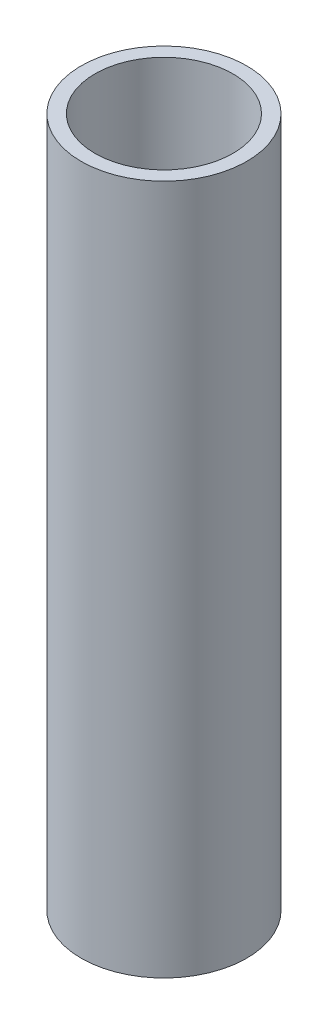
SolidWorks part; units mm, degrees
material "AISI 304"
ref_plane "Спереди" through (0, 0, 0) normal (0, 0, 1) x (1, 0, 0)
ref_plane "Сверху" through (0, 0, 0) normal (0, 1, 0) x (1, 0, 0)
ref_plane "Справа" through (0, 0, 0) normal (1, 0, 0) x (0, 0, -1)
ref_axis "ОсьX" through (-88.99, 0, 0) along (1, 0, 0)
ref_axis "ОсьZ" through (0, 55, 0) along (0, -1, 0)
ref_axis "ОсьY" through (0, 0, -88.99) along (0, 0, 1)
sketch "Эскиз1" plane through (0, 0, 0) normal (0, 0, 1) x (1, 0, 0)
  line L0 (-24, 200) -> (-24, 0)
  line L1 (0, 26.169) -> (0, -22.1581) construction
  dimension "D1" = 48
  dimension "D2" = 200
revolve "Повернуть-Тонкостенный1" add sketch "Эскиз1" angle 360 about L1 wall 4
